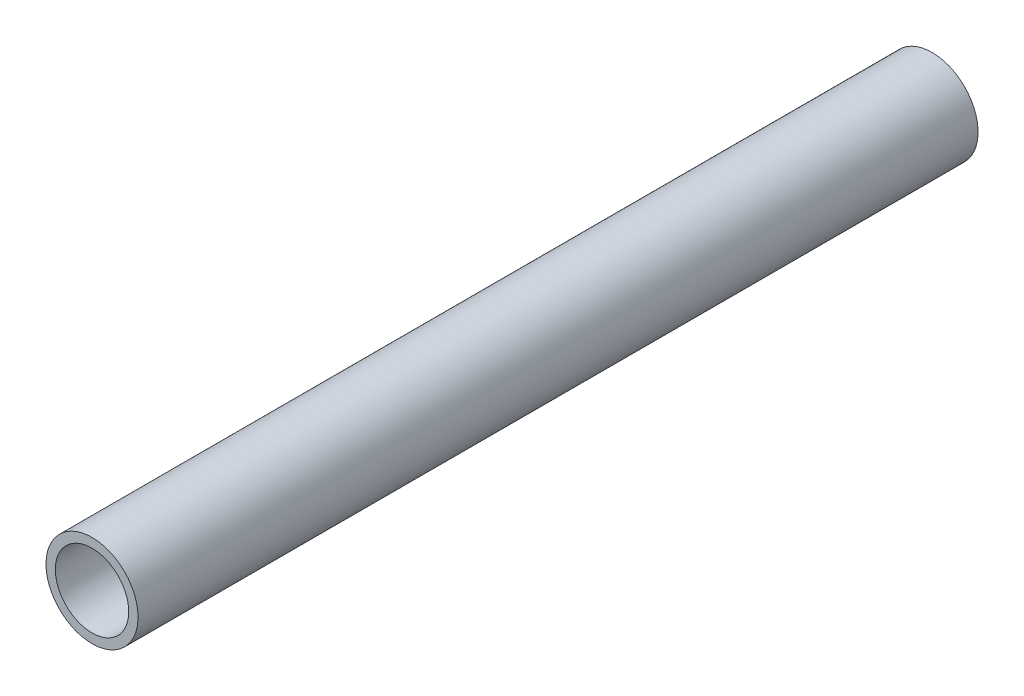
SolidWorks part; units mm, degrees
ref_plane "Front Plane" through (0, 0, 0) normal (0, 0, 1) x (1, 0, 0)
ref_plane "Top Plane" through (0, 0, 0) normal (0, 1, 0) x (1, 0, 0)
ref_plane "Right Plane" through (0, 0, 0) normal (1, 0, 0) x (0, 0, -1)
sketch "Sketch1" plane through (0, 0, 0) normal (0, 0, 1) x (1, 0, 0)
  circle A0 centre (0, 0) radius 16.7005
  dimension "Pipe OD" = 33.401
extrude "Extrude-Thin1" add sketch "Sketch1" along normal mid plane 304.8 thin thin type one direction reverse wall 3.3782
